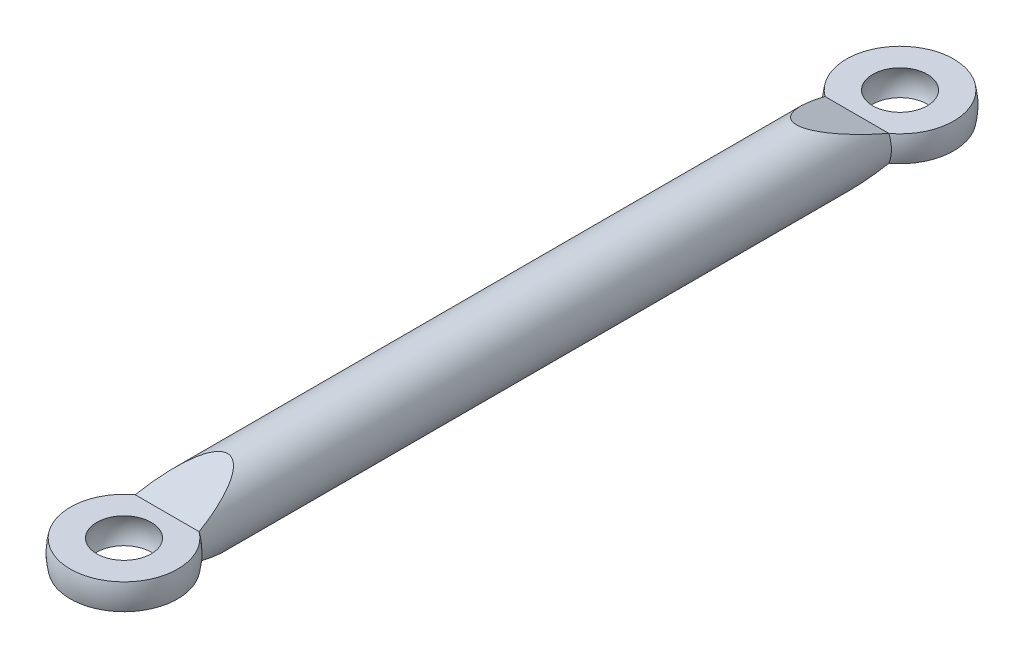
SolidWorks part; units mm, degrees
ref_plane "前视基准面" through (0, 0, 0) normal (0, 0, 1) x (1, 0, 0)
ref_plane "上视基准面" through (0, 0, 0) normal (0, 1, 0) x (1, 0, 0)
ref_plane "右视基准面" through (0, 0, 0) normal (1, 0, 0) x (0, 0, -1)
sketch "草图1" plane through (0, 0, 0) normal (0, 0, 1) x (1, 0, 0)
  circle A0 centre (0, 0) radius 4
  dimension "D1" = 8
extrude "凸台-拉伸1" add sketch "草图1" along normal mid plane 80
sketch "草图2" plane through (0, 0, 0) normal (0, 1, 0) x (1, 0, 0)
  line L0 (0, 51.4031) -> (0, 38.5969)
  line L1 (0, 0) -> (-4, 0) construction
  line L2 (-4, 40) -> (-4, -40) construction
  line L3 (0, -51.4031) -> (0, -38.5969)
  circle A0 centre (0, 45) radius 3.5
  circle A1 centre (0, 45) radius 6.4031
  circle A2 centre (0, -45) radius 6.4031
  circle A3 centre (0, -45) radius 3.5
  dimension "D1" = 45
  dimension "D2" = 7
revolve "旋转2" add sketch "草图2" angle 360 about L0 region at (4.4265, 0, -49.4265) region at (0.1432, 0, 49.9516)
sketch "草图3" plane through (0, 0, 0) normal (1, 0, 0) x (0, 0, -1)
  line L0 (0, 0) -> (-40, 0) construction
  line L1 (-40, 4) -> (-40, -4) construction
  line L2 (-33, 4) -> (-40, 1.5)
  line L3 (40, 4) -> (-40, 4) construction
  line L4 (-40, 1.5) -> (-53, 1.5)
  line L5 (-53, 1.5) -> (-53, 8)
  line L6 (-53, 8) -> (-33, 8)
  line L7 (-33, 8) -> (-33, 4)
  line L8 (-33, -8) -> (-33, -4)
  line L9 (-53, -8) -> (-33, -8)
  line L10 (-53, -1.5) -> (-53, -8)
  line L11 (-40, -1.5) -> (-53, -1.5)
  line L12 (-33, -4) -> (-40, -1.5)
  line L13 (0, 0) -> (0, -4) construction
  line L14 (33, -4) -> (40, -1.5)
  line L15 (40, -1.5) -> (53, -1.5)
  line L16 (53, -1.5) -> (53, -8)
  line L17 (53, -8) -> (33, -8)
  line L18 (33, -8) -> (33, -4)
  line L19 (33, 8) -> (33, 4)
  line L20 (53, 8) -> (33, 8)
  line L21 (53, 1.5) -> (53, 8)
  line L22 (40, 1.5) -> (53, 1.5)
  line L23 (33, 4) -> (40, 1.5)
  dimension "D1" = 33
  dimension "D2" = 20
  dimension "D3" = 6.5
  dimension "D4" = 4
extrude "切除-拉伸1" cut sketch "草图3" against normal through all both and the other way through all
ref_point "点1"
ref_point "点2"
ref_axis "基准轴1" through (0, 1.5, -45) along (0, 1, 0)
ref_axis "基准轴2" through (0, 1.5, 45) along (0, 1, 0)
